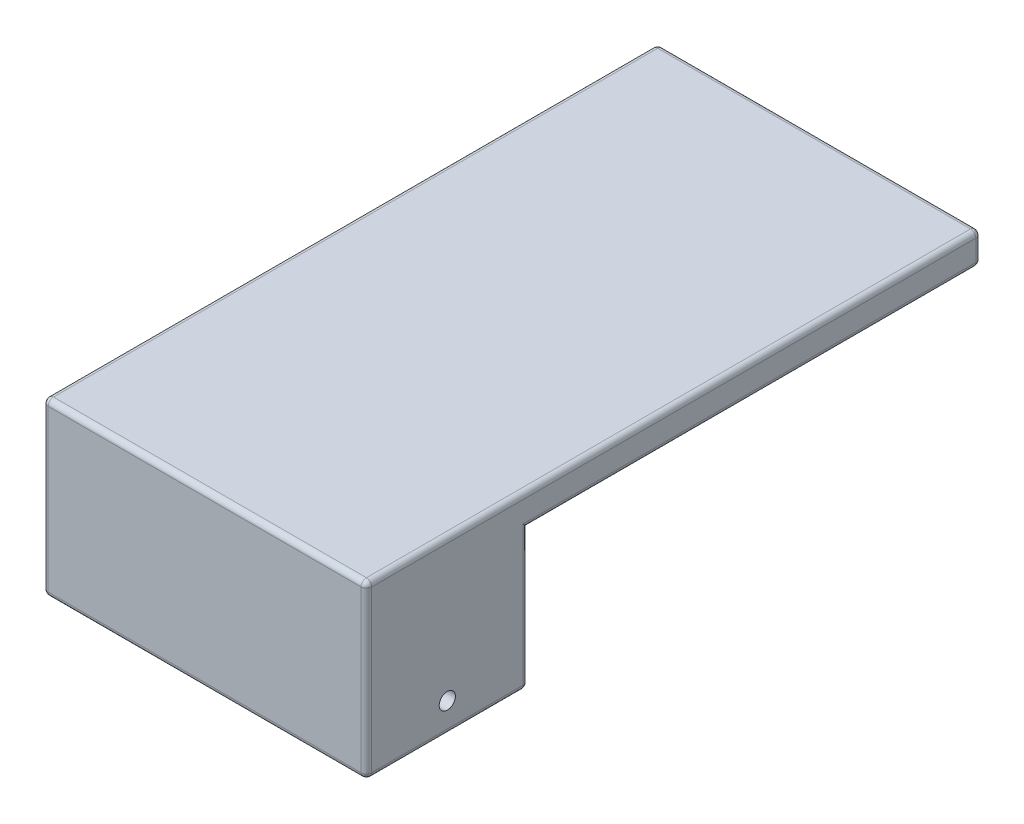
SolidWorks part; units mm, degrees
ref_plane "Front Plane" through (0, 0, 0) normal (0, 0, 1) x (1, 0, 0)
ref_plane "Top Plane" through (0, 0, 0) normal (0, 1, 0) x (1, 0, 0)
ref_plane "Right Plane" through (0, 0, 0) normal (1, 0, 0) x (0, 0, -1)
sketch "Sketch1" plane through (0, 0, 0) normal (1, 0, 0) x (0, 0, -1)
  line L0 (0, 375.5231) -> (0, -669.852) construction
  line L1 (-925.9292, 0) -> (1147.9054, 0) construction
  line L2 (-254, 122.0756) -> (711.2, 122.0756)
  line L3 (711.2, 122.0756) -> (711.2, 72.2916)
  line L4 (711.2, 72.2916) -> (0, 72.2916)
  line L5 (0, 72.2916) -> (0, -147.1644)
  line L6 (0, -147.1644) -> (-254, -147.1644)
  line L7 (-254, -147.1644) -> (-254, 122.0756)
  circle A0 centre (-127.0008, -100.4284) radius 12.7
  dimension "D5" = 25.4
  dimension "D1" = 965.2
  dimension "D2" = 269.24
  dimension "D3" = 49.784
  dimension "D4" = 254
extrude "Boss-Extrude1" add sketch "Sketch1" along normal mid plane 508
sketch "Sketch2" plane through (0, 72.2916, 0) normal (0, -1, 0) x (1, 0, 0)
  line L0 (0, -133.2604) -> (0, -662.7245) construction
  line L1 (229.8111, -648.97) -> (128.2111, -547.37) construction
  line L2 (-216.6031, -547.37) -> (-141.4191, -547.37)
  line L3 (-229.8111, -560.578) -> (-229.8111, -635.762)
  line L4 (-216.6031, -648.97) -> (-141.4191, -648.97)
  line L5 (-128.2111, -560.578) -> (-128.2111, -635.762)
  line L6 (-229.8111, -547.37) -> (-128.2111, -648.97) construction
  line L7 (-229.8111, -648.97) -> (-128.2111, -547.37) construction
  line L8 (229.8111, -547.37) -> (128.2111, -648.97) construction
  line L9 (128.2111, -560.578) -> (128.2111, -635.762)
  line L10 (216.6031, -648.97) -> (141.4191, -648.97)
  line L11 (229.8111, -560.578) -> (229.8111, -635.762)
  line L12 (216.6031, -547.37) -> (141.4191, -547.37)
  line L13 (254, -711.2) -> (-254, -711.2) construction
  arc A0 (-229.8111, -635.762) -> (-216.6031, -648.97) centre (-216.6031, -635.762) ccw
  arc A1 (-141.4191, -648.97) -> (-128.2111, -635.762) centre (-141.4191, -635.762) ccw
  arc A2 (-141.4191, -547.37) -> (-128.2111, -560.578) centre (-141.4191, -560.578) cw
  arc A3 (-216.6031, -547.37) -> (-229.8111, -560.578) centre (-216.6031, -560.578) ccw
  arc A4 (216.6031, -547.37) -> (229.8111, -560.578) centre (216.6031, -560.578) cw
  arc A5 (141.4191, -547.37) -> (128.2111, -560.578) centre (141.4191, -560.578) ccw
  arc A6 (141.4191, -648.97) -> (128.2111, -635.762) centre (141.4191, -635.762) cw
  arc A7 (229.8111, -635.762) -> (216.6031, -648.97) centre (216.6031, -635.762) cw
  point P3 (-179.0111, -598.17)
  point P36 (179.0111, -598.17)
  dimension "D1" = 13.208
  dimension "D2" = 101.6
  dimension "D3" = 101.6
  dimension "D4" = 62.23
extrude "Cut-Extrude2" cut sketch "Sketch2" against normal blind 3.81
fillet "Fillet1" radius 8.382 12 edges at (0, 122.0756, -711.2) (254, 122.0756, -228.6) (0, 122.0756, 254) (-254, 122.0756, -228.6) (-254, 97.1836, -711.2) (254, 97.1836, -711.2) (0, 72.2916, -711.2) (254, 72.2916, -355.6) (254, -37.4364, 0) (0, -147.1644, 254) (-254, -12.5444, 254) (254, -12.5444, 254)
fillet "Fillet2" radius 8.382 6 edges at (-251.545, -144.7094, 251.545) (251.545, -144.7094, 251.545) (-254, -147.1644, 122.809) (254, -147.1644, 127) (251.545, -147.1644, 2.455) (-4.191, -147.1644, 0)
